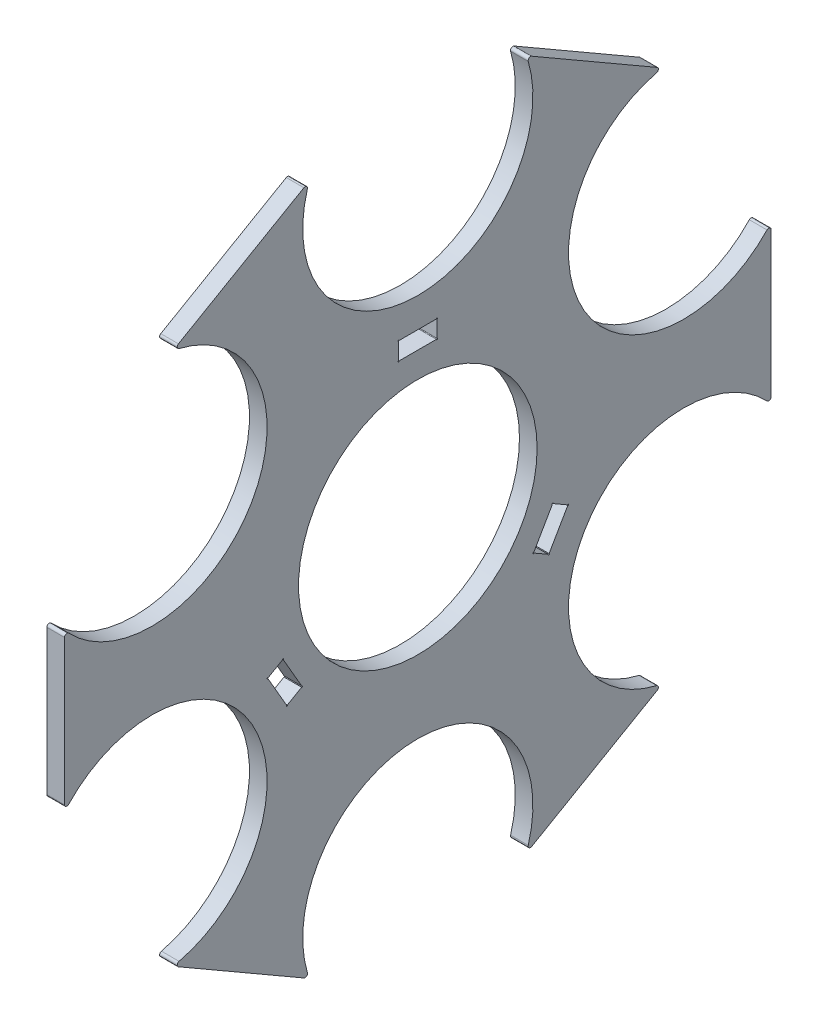
SolidWorks part; units mm, degrees
ref_plane "Front Plane" through (0, 0, 0) normal (0, 0, 1) x (1, 0, 0)
ref_plane "Top Plane" through (0, 0, 0) normal (0, 1, 0) x (1, 0, 0)
ref_plane "Right Plane" through (0, 0, 0) normal (1, 0, 0) x (0, 0, -1)
sketch "Sketch2" plane through (0, 0, 0) normal (1, 0, 0) x (0, 0, -1)
  line L0 (35.921, 114.3) -> (-35.921, 114.3) construction
  line L1 (81.0262, 88.2585) -> (35.921, 114.3)
  line L2 (116.9472, -26.0415) -> (116.9472, 26.0415)
  line L3 (35.921, -114.3) -> (81.0262, -88.2585)
  line L4 (-81.0262, -88.2585) -> (-35.921, -114.3)
  line L5 (-116.9472, 26.0415) -> (-116.9472, -26.0415)
  line L6 (-35.921, 114.3) -> (-81.0262, 88.2585)
  circle A0 centre (0, 0) radius 101.6 construction
  arc A1 (-35.921, 114.3) -> (35.921, 114.3) centre (0, 101.6) ccw
  arc A2 (81.0262, 88.2585) -> (116.9472, 26.0415) centre (87.9882, 50.8) ccw
  arc A3 (116.9472, -26.0415) -> (81.0262, -88.2585) centre (87.9882, -50.8) ccw
  arc A4 (35.921, -114.3) -> (-35.921, -114.3) centre (0, -101.6) ccw
  arc A5 (-81.0262, -88.2585) -> (-116.9472, -26.0415) centre (-87.9882, -50.8) ccw
  arc A6 (-116.9472, 26.0415) -> (-81.0262, 88.2585) centre (-87.9882, 50.8) ccw
  circle A7 centre (0, 0) radius 39.4875
  point P23 (0, 0)
  point P34 (0, 0)
  dimension "D1" = 203.2
  dimension "D2" = 114.3
  dimension "D3" = 76.2
  dimension "D6" = 78.9749
  dimension "D4" = 6
  dimension "D5" = 6
extrude "Boss-Extrude1" add sketch "Sketch2" along normal blind 5.842 contours A6 L5 A5 L4 A4 L3 A3 L2 A2 L1 A1 L6 region at (0, 30.1147, -52.1602)
fillet "Fillet1" radius 0.7937 12 edges at (2.921, -114.3, 35.921) (2.921, -114.3, -35.921) (2.921, -88.2585, -81.0262) (2.921, -26.0415, -116.9472) (2.921, 88.2585, -81.0262) (2.921, 26.0415, -116.9472) (2.921, -88.2585, 81.0262) (2.921, -26.0415, 116.9472) (2.921, 26.0415, 116.9472) (2.921, 88.2585, 81.0262) (2.921, 114.3, -35.921) (2.921, 114.3, 35.921)
sketch "Sketch3" plane through (5.842, 0, 0) normal (1, 0, 0) x (0, 0, -1)
  line L0 (0, 0) -> (0, 50.8) construction
  line L2 (6.1516, 53.721) -> (-6.1516, 53.721)
  line L3 (6.35, 53.5226) -> (6.35, 48.0774)
  line L4 (6.1516, 47.879) -> (-6.1516, 47.879)
  line L5 (-6.35, 53.5226) -> (-6.35, 48.0774)
  line L6 (6.35, 53.721) -> (-6.35, 47.879) construction
  line L7 (6.35, 47.879) -> (-6.35, 53.721) construction
  arc A0 (-6.1516, 53.721) -> (-6.35, 53.5226) centre (-6.35, 53.721) ccw
  arc A1 (-6.35, 48.0774) -> (-6.1516, 47.879) centre (-6.35, 47.879) ccw
  arc A2 (6.1516, 47.879) -> (6.35, 48.0774) centre (6.35, 47.879) ccw
  arc A3 (6.35, 53.5226) -> (6.1516, 53.721) centre (6.35, 53.721) ccw
  dimension "D4" = 0.3969
  dimension "D5" = 0.3969
  dimension "D6" = 0.3969
  dimension "D7" = 0.3969
  dimension "D1" = 50.8
  dimension "D2" = 12.7
  dimension "D3" = 5.842
extrude "Cut-Extrude2" cut sketch "Sketch3" against normal through all
pattern_circular "CirPattern1" count 3 every 120 about axis through (5.842, 0, 0) along (-1, 0, 0) of "Cut-Extrude2"
